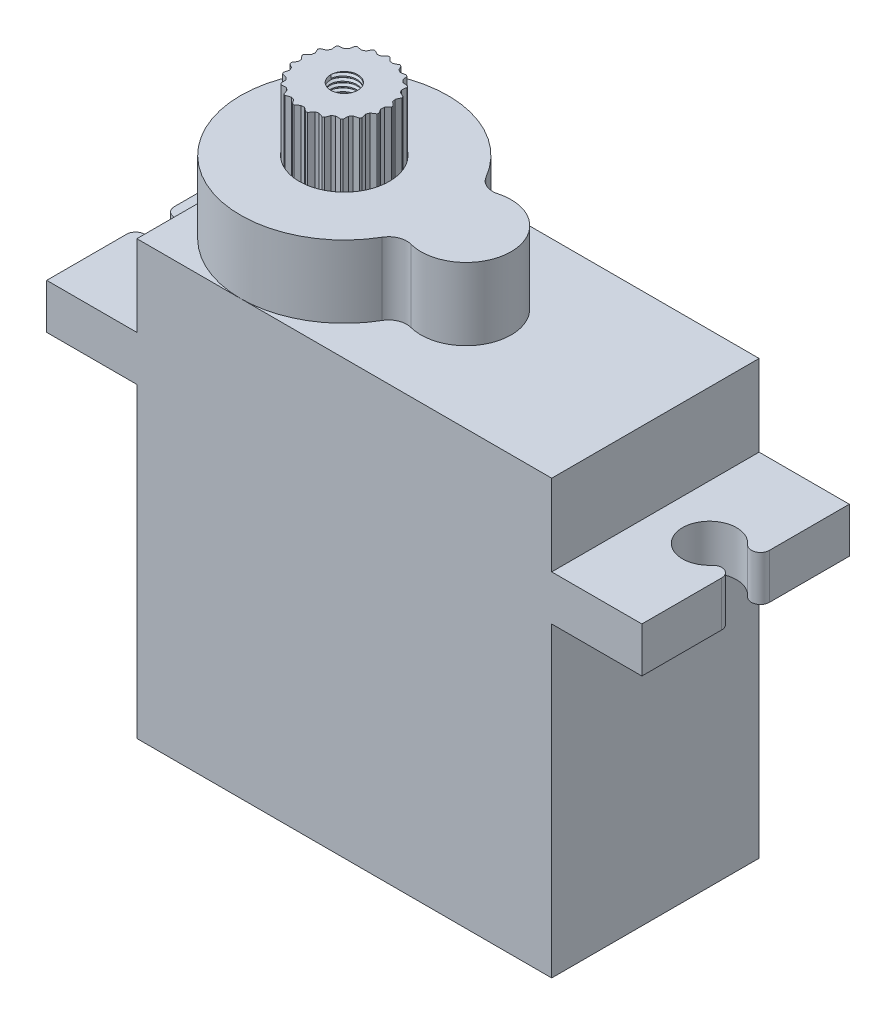
SolidWorks part; units mm, degrees
ref_plane "Front Plane" through (0, 0, 0) normal (0, 0, 1) x (1, 0, 0)
ref_plane "Top Plane" through (0, 0, 0) normal (0, 1, 0) x (1, 0, 0)
ref_plane "Right Plane" through (0, 0, 0) normal (1, 0, 0) x (0, 0, -1)
sketch "Sketch1" plane through (0, 0, 0) normal (0, 0, 1) x (1, 0, 0)
  line L0 (23, 17) -> (28, 17)
  line L1 (0, 0) -> (23, 0)
  line L2 (0, 0) -> (0, 17)
  line L3 (0, 24) -> (23, 24)
  line L4 (23, 0) -> (23, 17)
  line L5 (28, 17) -> (28, 19.5)
  line L6 (28, 19.5) -> (23, 19.5)
  line L7 (11.5, 24) -> (11.5, 0) construction
  line L8 (-5, 19.5) -> (0, 19.5)
  line L9 (-5, 17) -> (-5, 19.5)
  line L10 (0, 17) -> (-5, 17)
  line L11 (0, 19.5) -> (0, 24)
  line L12 (23, 19.5) -> (23, 24)
  dimension "D1" = 23
  dimension "D2" = 24
  dimension "D3" = 17
  dimension "D4" = 2.5
  dimension "D5" = 5
extrude "Boss-Extrude1" add sketch "Sketch1" along normal blind 11.5
sketch "Sketch2" plane through (0, 19.5, 0) normal (0, 1, 0) x (1, 0, 0)
  line L0 (-5, -5.75) -> (0, -5.75) construction
  line L1 (-5, -11.5) -> (-5, 0) construction
  line L2 (0, -11.5) -> (0, 0) construction
  line L3 (-5, -4.4271) -> (-5, -7.0729)
  arc A0 (-4.125, -6.7422) -> (-4.125, -4.7578) centre (-3, -5.75) ccw
  arc A1 (-5, -4.4271) -> (-4.125, -4.7578) centre (-4.5, -4.4271) ccw
  arc A2 (-5, -7.0729) -> (-4.125, -6.7422) centre (-4.5, -7.0729) cw
  dimension "D1" = 3
  dimension "D3" = 1
  dimension "D2" = 3
extrude "Cut-Extrude1" cut sketch "Sketch2" against normal blind 12
sketch "Sketch3" plane through (0, 19.5, 0) normal (0, 1, 0) x (1, 0, 0)
  line L0 (28, -5.75) -> (23, -5.75) construction
  line L1 (28, -11.5) -> (28, 0) construction
  line L2 (23, -11.5) -> (23, 0) construction
  line L3 (23, -11.5) -> (23, 0) construction
  line L4 (28, -4.4271) -> (28, -7.0729)
  arc A0 (27.125, -4.7578) -> (27.125, -6.7422) centre (26, -5.75) ccw
  arc A1 (27.125, -4.7578) -> (28, -4.4271) centre (27.5, -4.4271) ccw
  arc A2 (28, -7.0729) -> (27.125, -6.7422) centre (27.5, -7.0729) ccw
  dimension "D1" = 1
  dimension "D2" = 1
  dimension "D3" = 3
  dimension "D4" = 3
extrude "Cut-Extrude2" cut sketch "Sketch3" against normal blind 12
sketch "Sketch4" plane through (0, 24, 0) normal (0, 1, 0) x (1, 0, 0)
  line L0 (0, -11.5) -> (0, 0) construction
  line L1 (23, 0) -> (0, 0) construction
  line L2 (23, -11.5) -> (23, 0) construction
  line L3 (0, -5.75) -> (23, -5.75) construction
  line L4 (23, -11.5) -> (0, -11.5) construction
  arc A0 (10.727, -2.8705) -> (10.727, -8.6295) centre (5.75, -5.75) ccw
  arc A1 (11.8519, -8.1645) -> (11.8519, -3.3355) centre (12.5, -5.75) ccw
  arc A2 (10.727, -2.8705) -> (11.8519, -3.3355) centre (11.5926, -2.3697) ccw
  arc A3 (10.727, -8.6295) -> (11.8519, -8.1645) centre (11.5926, -9.1303) cw
  dimension "D1" = 11.5
  dimension "D2" = 5
  dimension "D3" = 10.5
  dimension "D4" = 5.75
  dimension "D5" = 2
extrude "Boss-Extrude2" add sketch "Sketch4" along normal blind 4
sketch "Sketch5" plane through (0, 28, 0) normal (0, 1, 0) x (1, 0, 0)
  circle A0 centre (5.75, -5.75) radius 2.5
  dimension "D1" = 5
extrude "Cut-Extrude3" cut sketch "Sketch5" against normal blind 6
sketch "Sketch6" plane through (0, 22, 0) normal (0, 1, 0) x (1, 0, 0)
  line L0 (5.75, -3.45) -> (5.75, -3.2625) construction
  line L1 (5.75, -3.2625) -> (5.8, -3.2625)
  line L2 (5.75, -3.2625) -> (5.7, -3.2625)
  line L3 (5.7, -3.2625) -> (5.5, -3.4636)
  line L4 (5.8, -3.2625) -> (6, -3.4636)
  line L7 (6.531, -3.3877) -> (6.6628, -3.6389)
  line L8 (6.4832, -3.373) -> (6.531, -3.3877)
  line L9 (6.4832, -3.373) -> (6.4354, -3.3583)
  line L10 (6.4354, -3.3583) -> (6.185, -3.4915)
  line L12 (7.1926, -3.7229) -> (7.2445, -4.0017)
  line L13 (7.1513, -3.6947) -> (7.1926, -3.7229)
  line L14 (7.1513, -3.6947) -> (7.11, -3.6666)
  line L15 (7.11, -3.6666) -> (6.8314, -3.7201)
  line L17 (7.726, -4.2382) -> (7.6934, -4.5199)
  line L18 (7.6948, -4.1991) -> (7.726, -4.2382)
  line L19 (7.6948, -4.1991) -> (7.6636, -4.16)
  line L20 (7.6636, -4.16) -> (7.3817, -4.129)
  line L22 (8.0838, -4.8878) -> (7.9697, -5.1474)
  line L23 (8.0656, -4.8412) -> (8.0838, -4.8878)
  line L24 (8.0656, -4.8412) -> (8.0473, -4.7947)
  line L25 (8.0473, -4.7947) -> (7.787, -4.682)
  line L27 (8.2343, -5.614) -> (8.0487, -5.8284)
  line L28 (8.2306, -5.5641) -> (8.2343, -5.614)
  line L29 (8.2306, -5.5641) -> (8.2268, -5.5142)
  line L30 (8.2268, -5.5142) -> (8.0113, -5.3298)
  line L32 (8.164, -6.3523) -> (7.9234, -6.5025)
  line L33 (8.1751, -6.3035) -> (8.164, -6.3523)
  line L34 (8.1751, -6.3035) -> (8.1863, -6.2548)
  line L35 (8.1863, -6.2548) -> (8.0347, -6.015)
  line L37 (7.8792, -7.0371) -> (7.6051, -7.1097)
  line L38 (7.9042, -6.9938) -> (7.8792, -7.0371)
  line L39 (7.9042, -6.9938) -> (7.9292, -6.9505)
  line L40 (7.9292, -6.9505) -> (7.8551, -6.6767)
  line L42 (7.4053, -7.6075) -> (7.1219, -7.5961)
  line L43 (7.4419, -7.5735) -> (7.4053, -7.6075)
  line L44 (7.4419, -7.5735) -> (7.4786, -7.5395)
  line L45 (7.4786, -7.5395) -> (7.4884, -7.256)
  line L47 (6.7842, -8.0129) -> (6.5168, -7.9184)
  line L48 (6.8293, -7.9912) -> (6.7842, -8.0129)
  line L49 (6.8293, -7.9912) -> (6.8743, -7.9695)
  line L50 (6.8743, -7.9695) -> (6.9673, -7.7015)
  line L52 (6.0713, -8.2172) -> (5.8436, -8.0481)
  line L53 (6.1207, -8.2097) -> (6.0713, -8.2172)
  line L54 (6.1207, -8.2097) -> (6.1702, -8.2023)
  line L55 (6.1702, -8.2023) -> (6.338, -7.9736)
  line L57 (5.3298, -8.2023) -> (5.162, -7.9736)
  line L58 (5.3793, -8.2097) -> (5.3298, -8.2023)
  line L59 (5.3793, -8.2097) -> (5.4287, -8.2172)
  line L60 (5.4287, -8.2172) -> (5.6564, -8.0481)
  line L62 (4.6257, -7.9695) -> (4.5327, -7.7015)
  line L63 (4.6707, -7.9912) -> (4.6257, -7.9695)
  line L64 (4.6707, -7.9912) -> (4.7158, -8.0129)
  line L65 (4.7158, -8.0129) -> (4.9832, -7.9184)
  line L67 (4.0214, -7.5395) -> (4.0116, -7.256)
  line L68 (4.0581, -7.5735) -> (4.0214, -7.5395)
  line L69 (4.0581, -7.5735) -> (4.0947, -7.6075)
  line L70 (4.0947, -7.6075) -> (4.3781, -7.5961)
  line L72 (3.5708, -6.9505) -> (3.6449, -6.6767)
  line L73 (3.5958, -6.9938) -> (3.5708, -6.9505)
  line L74 (3.5958, -6.9938) -> (3.6208, -7.0371)
  line L75 (3.6208, -7.0371) -> (3.8949, -7.1097)
  line L77 (3.3137, -6.2548) -> (3.4653, -6.015)
  line L78 (3.3249, -6.3035) -> (3.3137, -6.2548)
  line L79 (3.3249, -6.3035) -> (3.336, -6.3523)
  line L80 (3.336, -6.3523) -> (3.5766, -6.5025)
  line L82 (3.2732, -5.5142) -> (3.4887, -5.3298)
  line L83 (3.2694, -5.5641) -> (3.2732, -5.5142)
  line L84 (3.2694, -5.5641) -> (3.2657, -5.614)
  line L85 (3.2657, -5.614) -> (3.4513, -5.8284)
  line L87 (3.4527, -4.7947) -> (3.713, -4.682)
  line L88 (3.4344, -4.8412) -> (3.4527, -4.7947)
  line L89 (3.4344, -4.8412) -> (3.4162, -4.8878)
  line L90 (3.4162, -4.8878) -> (3.5303, -5.1474)
  line L92 (3.8364, -4.16) -> (4.1183, -4.129)
  line L93 (3.8052, -4.1991) -> (3.8364, -4.16)
  line L94 (3.8052, -4.1991) -> (3.774, -4.2382)
  line L95 (3.774, -4.2382) -> (3.8066, -4.5199)
  line L97 (4.39, -3.6666) -> (4.6686, -3.7201)
  line L98 (4.3487, -3.6947) -> (4.39, -3.6666)
  line L99 (4.3487, -3.6947) -> (4.3074, -3.7229)
  line L100 (4.3074, -3.7229) -> (4.2555, -4.0017)
  line L102 (5.0646, -3.3583) -> (5.315, -3.4915)
  line L103 (5.0168, -3.373) -> (5.0646, -3.3583)
  line L104 (5.0168, -3.373) -> (4.969, -3.3877)
  line L105 (4.969, -3.3877) -> (4.8372, -3.6389)
  arc A2 (4.8372, -3.6389) -> (4.6686, -3.7201) centre (5.75, -5.75) ccw
  arc A4 (6.185, -3.4915) -> (6, -3.4636) centre (5.75, -5.75) ccw
  arc A5 (6.8314, -3.7201) -> (6.6628, -3.6389) centre (5.75, -5.75) ccw
  arc A6 (7.3817, -4.129) -> (7.2445, -4.0017) centre (5.75, -5.75) ccw
  arc A7 (7.787, -4.682) -> (7.6934, -4.5199) centre (5.75, -5.75) ccw
  arc A8 (8.0113, -5.3298) -> (7.9697, -5.1474) centre (5.75, -5.75) ccw
  arc A9 (8.0347, -6.015) -> (8.0487, -5.8284) centre (5.75, -5.75) ccw
  arc A10 (7.8551, -6.6767) -> (7.9234, -6.5025) centre (5.75, -5.75) ccw
  arc A11 (7.4884, -7.256) -> (7.6051, -7.1097) centre (5.75, -5.75) ccw
  arc A12 (6.9673, -7.7015) -> (7.1219, -7.5961) centre (5.75, -5.75) ccw
  arc A13 (6.338, -7.9736) -> (6.5168, -7.9184) centre (5.75, -5.75) ccw
  arc A14 (5.6564, -8.0481) -> (5.8436, -8.0481) centre (5.75, -5.75) ccw
  arc A15 (4.9832, -7.9184) -> (5.162, -7.9736) centre (5.75, -5.75) ccw
  arc A16 (3.8949, -7.1097) -> (4.0116, -7.256) centre (5.75, -5.75) ccw
  arc A17 (4.3781, -7.5961) -> (4.5327, -7.7015) centre (5.75, -5.75) ccw
  arc A18 (3.5766, -6.5025) -> (3.6449, -6.6767) centre (5.75, -5.75) ccw
  arc A19 (3.4513, -5.8284) -> (3.4653, -6.015) centre (5.75, -5.75) ccw
  arc A20 (3.5303, -5.1474) -> (3.4887, -5.3298) centre (5.75, -5.75) ccw
  arc A21 (3.8066, -4.5199) -> (3.713, -4.682) centre (5.75, -5.75) ccw
  arc A22 (4.2555, -4.0017) -> (4.1183, -4.129) centre (5.75, -5.75) ccw
  arc A23 (5.5, -3.4636) -> (5.315, -3.4915) centre (5.75, -5.75) ccw
  dimension "D1" = 4.6
  dimension "D2" = 0.05
  dimension "D3" = 0.05
  dimension "D4" = 0.5
  dimension "D5" = 21
  dimension "D6" = 0.1875
  dimension "D7" = 0.2011
extrude "Boss-Extrude4" add sketch "Sketch6" along normal blind 9.5
sketch "Sketch11" plane through (0, 31.5, 0) normal (0, 1, 0) x (1, 0, 0)
  circle A0 centre (5.75, -5.75) radius 0.75
  dimension "D1" = 1.5
extrude "Cut-Extrude6" cut sketch "Sketch11" against normal blind 6
thread "Thread2" pitch 0.25 method cut profile "Thread Profile2" start angle 0, offset 0, length 6, pitch 0.25, diameter 1.5
ref_plane "Plane3" through (5, 31.5, 5.75) normal (0, 0, 1) x (-1, 0, 0)
sketch "Thread Profile2" plane through (5, 31.5, 5.75) normal (0, 0, 1) x (-1, 0, 0)
  line L0 (0, 0) -> (0, 0.25) construction
  line L1 (0, 0) -> (0.1353, 0.0781)
  line L2 (0.1353, 0.0781) -> (0.1353, 0.1094)
  line L3 (0.1353, 0.1094) -> (0, 0.1875)
  line L4 (0.1353, 0.0937) -> (0, 0.0937) construction
  line L11 (0, 0) -> (0, 0.1875)
  point P2 (0, 0)
  dimension "Pitch" = 0.25
  dimension "Profile_Angle" = 60
  dimension "Profile_Land" = 0.0312
  dimension "Profile_Height" = 0.1353
